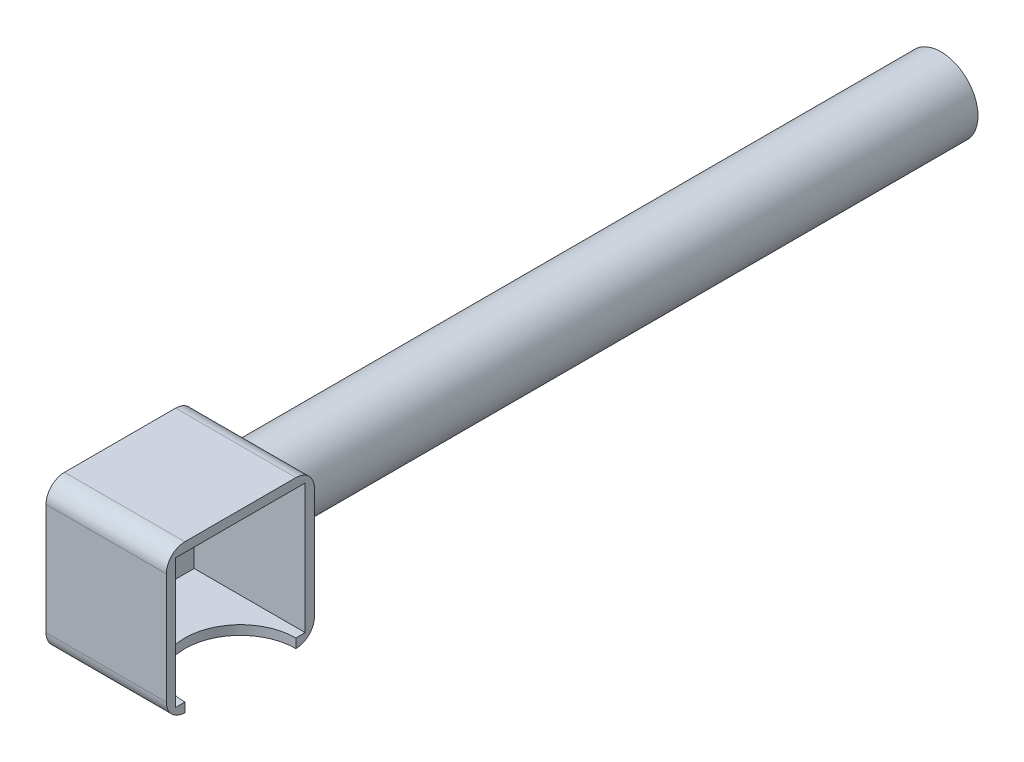
SolidWorks part; units mm, degrees
material "PLA"
ref_plane "Front Plane" through (0, 0, 0) normal (0, 0, 1) x (1, 0, 0)
ref_plane "Top Plane" through (0, 0, 0) normal (0, 1, 0) x (1, 0, 0)
ref_plane "Right Plane" through (0, 0, 0) normal (1, 0, 0) x (0, 0, -1)
sketch "Sketch2" plane through (0, 0, 0) normal (0, 0, 1) x (1, 0, 0)
  circle A0 centre (0, 0) radius 10
  dimension "D1" = 20
extrude "Boss-Extrude1" add sketch "Sketch2" along normal blind 199.71
ref_plane "Plane1" through (0, -10, 0) normal (0, -1, 0) x (-1, 0, 0)
sketch "Sketch4" plane through (0, -10, 0) normal (0, -1, 0) x (-1, 0, 0)
  line L0 (-4.55, -23.7884) -> (-4.55, -4.7884)
  line L1 (4.55, -51.2116) -> (-4.55, -51.2116)
  line L2 (4.55, -51.2116) -> (4.55, -32.2116)
  line L3 (4.55, -4.7884) -> (-4.55, -4.7884)
  line L4 (-4.55, -51.2116) -> (-4.55, -32.2116)
  line L5 (4.55, -51.2116) -> (-4.55, -4.7884) construction
  line L6 (4.55, -4.7884) -> (-4.55, -51.2116) construction
  line L7 (4.55, -23.7884) -> (4.55, -4.7884)
  arc A0 (-4.55, -23.7884) -> (-4.55, -32.2116) centre (0, -28) ccw
  arc A1 (4.55, -32.2116) -> (4.55, -23.7884) centre (0, -28) ccw
  dimension "D1" = 12.4
  dimension "D2" = 19
  dimension "D3" = 9.1
  dimension "D4" = 28
extrude "Cut-Extrude2" cut sketch "Sketch4" against normal blind 4.55
sketch "Sketch5" plane through (0, 0, 199.71) normal (0, 0, 1) x (1, 0, 0)
  line L1 (-10, -20) -> (22.5, -20)
  line L2 (-10, -20) -> (-10, 20)
  line L3 (-10, 20) -> (22.5, 20)
  line L4 (22.5, -20) -> (22.5, 20)
  point P0 (0, 0)
  point P6 (22.5, 0)
  dimension "D1" = 40
  dimension "D2" = 10
  dimension "D3" = 22.5
extrude "Boss-Extrude2" add sketch "Sketch5" along normal blind 40
sketch "Sketch10" plane through (22.5, 0, 0) normal (1, 0, 0) x (0, 0, -1)
  line L0 (-239.71, 20) -> (-199.71, 20) construction
  line L1 (-237.21, -17.5) -> (-202.21, -17.5)
  line L2 (-237.21, -17.5) -> (-237.21, 17.5)
  line L3 (-237.21, 17.5) -> (-202.21, 17.5)
  line L4 (-202.21, -17.5) -> (-202.21, 17.5)
  line L5 (-237.21, -17.5) -> (-202.21, 17.5) construction
  line L6 (-237.21, 17.5) -> (-202.21, -17.5) construction
  point P0 (-219.71, 0)
  point P8 (-219.71, 20)
  dimension "D1" = 35
  dimension "D2" = 35
extrude "Cut-Extrude3" cut sketch "Sketch10" against normal blind 30
sketch "Sketch11" plane through (-7.5, 0, 0) normal (1, 0, 0) x (0, 0, -1)
  line L1 (-229.71, -7.5) -> (-209.71, -7.5)
  line L2 (-229.71, -7.5) -> (-229.71, 7.5)
  line L3 (-229.71, 7.5) -> (-209.71, 7.5)
  line L4 (-209.71, -7.5) -> (-209.71, 7.5)
  line L5 (-229.71, -7.5) -> (-209.71, 7.5) construction
  line L6 (-229.71, 7.5) -> (-209.71, -7.5) construction
  line L8 (-237.21, 17.5) -> (-237.21, -17.5) construction
  line L12 (-202.21, -17.5) -> (-202.21, 17.5) construction
  point P0 (-219.71, 0)
  point P19 (-237.21, 0)
  dimension "D1" = 20
  dimension "D2" = 15
  dimension "D3" = 17.5
extrude "Cut-Extrude4" cut sketch "Sketch11" against normal up to surface (2.5 mm away) up to face at (-10, 0, 215.71)
fillet "Fillet1" radius 5 4 edges at (6.25, 20, 199.71) (6.25, 20, 239.71) (6.25, -20, 199.71) (6.25, -20, 239.71)
sketch "Sketch12" plane through (0, 0, 0) normal (0, 0, -1) x (-1, 0, 0)
  circle A0 centre (0, 0) radius 5
  dimension "D1" = 10
extrude "Cut-Extrude5" cut sketch "Sketch12" against normal up to surface (199.71 mm away) up to face at (4.1667, 0, 199.71)
extrude "Cut-Extrude6" cut sketch "Sketch2<2>" along normal blind 8
sketch "Sketch2<2>" plane through (0, 0, 0) normal (0, 0, 1) x (1, 0, 0) same geometry as "Sketch2"
sketch "Sketch15" plane through (0, 0, 8) normal (0, 0, -1) x (-1, 0, 0)
  line L0 (4.55, -8.9049) -> (4.55, -5.45) construction
  line L1 (-4.55, -5.45) -> (4.55, -5.45) construction
  line L2 (-4.55, -5.45) -> (-4.55, -8.9049) construction
  line L3 (4.55, -8.9049) -> (4.55, -5.45)
  line L4 (-4.55, -5.45) -> (4.55, -5.45)
  line L5 (-4.55, -5.45) -> (-4.55, -8.9049)
  arc A0 (-4.55, -8.9049) -> (4.55, -8.9049) centre (0, 0) ccw construction
  arc A1 (-4.55, -8.9049) -> (4.55, -8.9049) centre (0, 0) ccw
extrude "Boss-Extrude3" add sketch "Sketch15" against normal blind 1
sketch "Sketch16" plane through (0, -20, 0) normal (0, -1, 0) x (1, 0, 0)
  line L0 (22.5, 234.71) -> (22.5, 204.71) construction
  circle A0 centre (22.5, 219.71) radius 15
extrude "Cut-Extrude7" cut sketch "Sketch16" against normal blind 10
